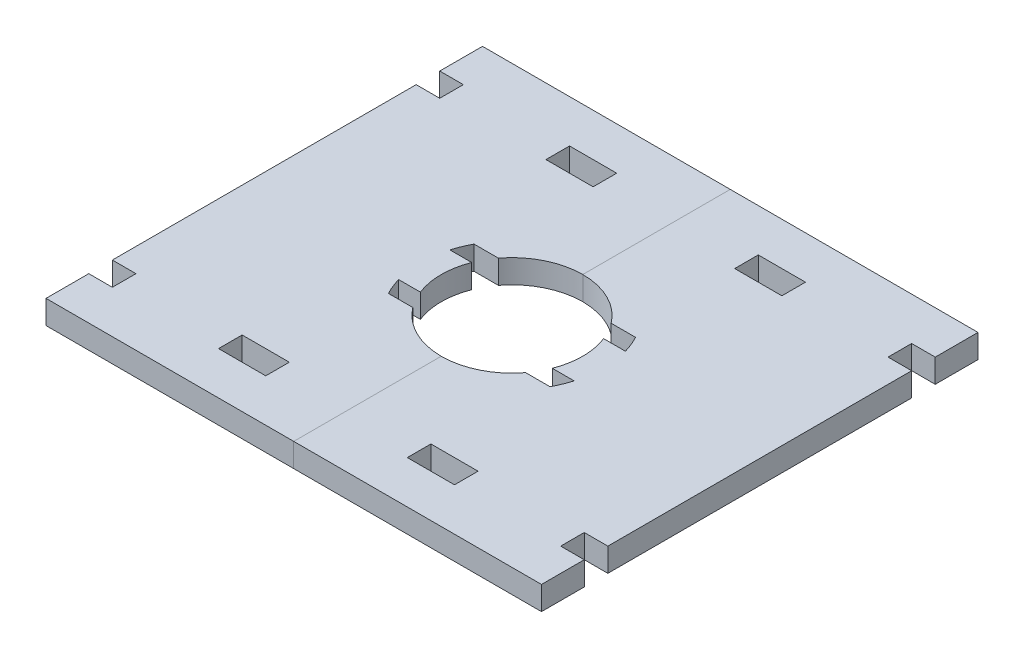
SolidWorks part; units mm, degrees
ref_plane "Front Plane" through (0, 0, 0) normal (0, 0, 1) x (1, 0, 0)
ref_plane "Top Plane" through (0, 0, 0) normal (0, 1, 0) x (1, 0, 0)
ref_plane "Right Plane" through (0, 0, 0) normal (1, 0, 0) x (0, 0, -1)
sketch "Sketch1" plane through (0, 0, 0) normal (0, 1, 0) x (1, 0, 0)
  line L0 (-15.5, 7.25) -> (-13.6999, 7.25) construction
  line L1 (-13.6999, -7.25) -> (-9.5623, -7.25)
  line L2 (-15.5, -7.25) -> (-15.5, -4.35) construction
  line L3 (-13.6999, 7.25) -> (-9.5623, 7.25)
  line L4 (15.5, 4.35) -> (15.5, 7.25) construction
  line L5 (-14.04, -6.5671) -> (-10.8697, -5.0842) construction
  line L6 (-14.04, 6.5671) -> (-10.8697, 5.0842) construction
  line L7 (-14.8771, -4.35) -> (-11.1838, -4.35)
  line L8 (-15.5, -4.35) -> (-15.5, 0) construction
  line L9 (-14.8771, 4.35) -> (-11.1838, 4.35)
  line L10 (15.5, 0) -> (15.5, 4.35) construction
  line L11 (-14.9234, -4.1882) -> (14.9234, 4.1882) construction
  line L12 (-14.9234, 4.1882) -> (14.9234, -4.1882) construction
  line L13 (-15.5, 7.25) -> (-14.04, 6.5671) construction
  line L14 (-15.5, 4.35) -> (-15.5, 7.25) construction
  line L15 (-15.5, 4.35) -> (-14.8771, 4.35) construction
  line L16 (-15.5, 4.35) -> (-14.9234, 4.1882) construction
  line L17 (-15.5, 0) -> (-15.5, 4.35) construction
  line L18 (-15.5, 0) -> (-15.5, 4.35) construction
  line L19 (-15.5, -4.35) -> (-15.5, 0) construction
  line L20 (-15.5, -4.35) -> (-14.9234, -4.1882) construction
  line L21 (-15.5, -4.35) -> (-14.8771, -4.35) construction
  line L22 (-15.5, -7.25) -> (-14.04, -6.5671) construction
  line L23 (-15.5, -7.25) -> (-13.6999, -7.25) construction
  line L24 (15.5, -7.25) -> (15.5, -4.35) construction
  line L25 (14.04, -6.5671) -> (15.5, -7.25) construction
  line L26 (13.6999, -7.25) -> (15.5, -7.25) construction
  line L27 (15.5, -4.35) -> (15.5, 0) construction
  line L28 (15.5, -4.35) -> (15.5, 0) construction
  line L29 (15.5, 0) -> (15.5, 4.35) construction
  line L30 (14.9234, 4.1882) -> (15.5, 4.35) construction
  line L31 (14.8771, 4.35) -> (15.5, 4.35) construction
  line L32 (13.6999, 7.25) -> (15.5, 7.25) construction
  line L33 (14.9234, -4.1882) -> (15.5, -4.35) construction
  line L34 (14.8771, -4.35) -> (15.5, -4.35) construction
  line L35 (-9.5623, 7.25) -> (9.5623, 7.25) construction
  line L36 (9.5623, 7.25) -> (13.6999, 7.25)
  line L37 (-9.3, 4.35) -> (9.3, 4.35) construction
  line L38 (11.1838, 4.35) -> (14.8771, 4.35)
  line L39 (-10.8697, 5.0842) -> (-9.3, 4.35) construction
  line L40 (-9.3, 4.35) -> (9.3, -4.35) construction
  line L41 (-11.1838, 4.35) -> (-9.3, 4.35) construction
  line L42 (-9.5623, -7.25) -> (9.5623, -7.25) construction
  line L43 (9.5623, -7.25) -> (13.6999, -7.25)
  line L44 (-9.3, -4.35) -> (9.3, -4.35) construction
  line L45 (11.1838, -4.35) -> (14.8771, -4.35)
  line L46 (-10.8697, -5.0842) -> (-9.3, -4.35) construction
  line L47 (-9.3, -4.35) -> (9.3, 4.35) construction
  line L48 (-11.1838, -4.35) -> (-9.3, -4.35) construction
  line L49 (9.3, -4.35) -> (11.1838, -4.35) construction
  line L50 (9.3, -4.35) -> (10.8697, -5.0842) construction
  line L51 (10.8697, -5.0842) -> (14.04, -6.5671) construction
  line L52 (9.3, 4.35) -> (11.1838, 4.35) construction
  line L53 (9.3, 4.35) -> (10.8697, 5.0842) construction
  line L54 (10.8697, 5.0842) -> (15.5, 7.25) construction
  arc A0 (-11.1838, 4.35) -> (-11.1838, -4.35) centre (0, 0) ccw
  arc A1 (-13.6999, 7.25) -> (-14.9234, 4.1882) centre (0, 0) ccw
  arc A2 (13.6999, 7.25) -> (-13.6999, 7.25) centre (0, 0) ccw construction
  arc A3 (-13.6999, -7.25) -> (13.6999, -7.25) centre (0, 0) ccw construction
  arc A4 (13.6999, -7.25) -> (14.9234, -4.1882) centre (0, 0) ccw
  arc A5 (15.5, 0) -> (14.9234, 4.1882) centre (0, 0) ccw construction
  arc A6 (14.9234, 4.1882) -> (13.6999, 7.25) centre (0, 0) ccw
  arc A7 (14.9234, -4.1882) -> (15.5, 0) centre (0, 0) ccw construction
  arc A8 (-14.9234, 4.1882) -> (-15.5, 0) centre (0, 0) ccw construction
  arc A9 (-14.9234, -4.1882) -> (-13.6999, -7.25) centre (0, 0) ccw
  arc A10 (-15.5, 0) -> (-14.9234, -4.1882) centre (0, 0) ccw construction
  arc A11 (-9.5623, 7.25) -> (-10.8697, 5.0842) centre (0, 0) ccw construction
  arc A12 (-10.8697, 5.0842) -> (-11.1838, 4.35) centre (0, 0) ccw construction
  arc A13 (-10.8697, -5.0842) -> (-9.5623, -7.25) centre (0, 0) ccw construction
  arc A14 (-9.5623, -7.25) -> (9.5623, -7.25) centre (0, 0) ccw
  arc A15 (-11.1838, -4.35) -> (-10.8697, -5.0842) centre (0, 0) ccw construction
  arc A16 (10.8697, -5.0842) -> (11.1838, -4.35) centre (0, 0) ccw construction
  arc A17 (11.1838, -4.35) -> (-9.5623, 7.25) centre (0, 0) ccw
  arc A18 (9.5623, -7.25) -> (10.8697, -5.0842) centre (0, 0) ccw construction
  dimension "D1" = 24
  dimension "D2" = 31
  dimension "D3" = 14.5
  dimension "D4" = 8.7
sketch "Sketch2" plane through (0, 0, 0) normal (0, 1, 0) x (1, 0, 0)
  line L0 (11.1838, -4.35) -> (14.8771, -4.35) construction
  line L1 (-13.6999, 7.25) -> (-9.5623, 7.25) construction
  line L2 (-14.8771, -4.35) -> (-11.1838, -4.35) construction
  line L3 (-14.8771, 4.35) -> (-11.1838, 4.35) construction
  line L4 (9.5623, -7.25) -> (13.6999, -7.25) construction
  line L5 (-13.6999, -7.25) -> (-9.5623, -7.25) construction
  line L6 (9.5623, 7.25) -> (13.6999, 7.25) construction
  line L7 (11.1838, 4.35) -> (14.8771, 4.35) construction
  line L8 (11.1838, -4.35) -> (14.8771, -4.35)
  line L9 (-13.6999, 7.25) -> (-9.5623, 7.25)
  line L10 (-14.8771, -4.35) -> (-11.1838, -4.35)
  line L11 (-14.8771, 4.35) -> (-11.1838, 4.35)
  line L12 (9.5623, -7.25) -> (13.6999, -7.25)
  line L13 (-13.6999, -7.25) -> (-9.5623, -7.25)
  line L14 (9.5623, 7.25) -> (13.6999, 7.25)
  line L15 (11.1838, 4.35) -> (14.8771, 4.35)
  line L17 (-42, -37) -> (42, -37)
  line L18 (-42, -37) -> (-42, 37)
  line L19 (-42, 37) -> (42, 37)
  line L20 (42, -37) -> (42, 37)
  line L21 (-42, -37) -> (42, 37) construction
  line L22 (-42, 37) -> (42, -37) construction
  arc A0 (11.1838, -4.35) -> (-9.5623, 7.25) centre (0, 0) ccw construction
  arc A1 (-13.6999, 7.25) -> (-14.9234, 4.1882) centre (0, 0) ccw construction
  arc A2 (-11.1838, 4.35) -> (-11.1838, -4.35) centre (0, 0) ccw construction
  arc A3 (13.6999, -7.25) -> (14.9234, -4.1882) centre (0, 0) ccw construction
  arc A4 (-9.5623, -7.25) -> (9.5623, -7.25) centre (0, 0) ccw construction
  arc A5 (-14.9234, -4.1882) -> (-13.6999, -7.25) centre (0, 0) ccw construction
  arc A6 (14.9234, 4.1882) -> (13.6999, 7.25) centre (0, 0) ccw construction
  arc A7 (11.1838, -4.35) -> (-9.5623, 7.25) centre (0, 0) ccw
  arc A8 (-13.6999, 7.25) -> (-14.9234, 4.1882) centre (0, 0) ccw
  arc A9 (-11.1838, 4.35) -> (-11.1838, -4.35) centre (0, 0) ccw
  arc A10 (13.6999, -7.25) -> (14.9234, -4.1882) centre (0, 0) ccw
  arc A11 (-9.5623, -7.25) -> (9.5623, -7.25) centre (0, 0) ccw
  arc A12 (-14.9234, -4.1882) -> (-13.6999, -7.25) centre (0, 0) ccw
  arc A13 (14.9234, 4.1882) -> (13.6999, 7.25) centre (0, 0) ccw
  dimension "D1" = 84
  dimension "D2" = 74
extrude "Boss-Extrude1" add sketch "Sketch2" along normal blind 4 contours L17 L20 L19 L18 A13 L15 A7 L8 A10 L12 A11 L13 A12 L10 A9 L11 A8 L9 L14 region at (-40.8805, 0, 0)
split "Split1" trim tools "Right Plane" bodies to split 101 resulting bodies 102 103
sketch "Sketch4" plane through (0, 4, 0) normal (0, 1, 0) x (1, 0, 0)
  line L0 (0, -18.5) -> (42, -18.5) construction
  line L2 (42, -37) -> (42, 37) construction
  line L3 (0, -18.5) -> (0, -37) construction
  line L4 (-42, -37) -> (-42, 37) construction
  line L5 (-20, -29.75) -> (-12, -29.75)
  line L6 (-20, -29.75) -> (-20, -25.75)
  line L7 (-20, -25.75) -> (-12, -25.75)
  line L8 (-12, -29.75) -> (-12, -25.75)
  line L9 (-20, -29.75) -> (-12, -25.75) construction
  line L10 (-20, -25.75) -> (-12, -29.75) construction
  line L11 (-42, -29.75) -> (-38, -29.75)
  line L12 (-42, -29.75) -> (-42, -25.75)
  line L13 (-42, -25.75) -> (-38, -25.75)
  line L14 (-38, -29.75) -> (-38, -25.75)
  line L15 (-42, -29.75) -> (-38, -25.75) construction
  line L16 (-42, -25.75) -> (-38, -29.75) construction
  line L17 (0, 0) -> (0, -37) construction
  line L33 (42, -25.75) -> (38, -29.75) construction
  line L34 (42, -29.75) -> (38, -25.75) construction
  line L35 (20, -25.75) -> (12, -29.75) construction
  line L36 (20, -29.75) -> (12, -25.75) construction
  line L45 (38, -29.75) -> (38, -25.75)
  line L46 (42, -25.75) -> (38, -25.75)
  line L47 (42, -29.75) -> (42, -25.75)
  line L48 (42, -29.75) -> (38, -29.75)
  line L49 (12, -29.75) -> (12, -25.75)
  line L50 (20, -25.75) -> (12, -25.75)
  line L51 (20, -29.75) -> (20, -25.75)
  line L52 (20, -29.75) -> (12, -29.75)
  line L53 (-2.2, 0) -> (2.2, 0) construction
  line L54 (20, 29.75) -> (12, 25.75) construction
  line L55 (20, 25.75) -> (12, 29.75) construction
  line L56 (42, 29.75) -> (38, 25.75) construction
  line L57 (42, 25.75) -> (38, 29.75) construction
  line L58 (20, 29.75) -> (12, 29.75)
  line L59 (20, 29.75) -> (20, 25.75)
  line L60 (20, 25.75) -> (12, 25.75)
  line L61 (12, 29.75) -> (12, 25.75)
  line L62 (42, 29.75) -> (38, 29.75)
  line L63 (42, 29.75) -> (42, 25.75)
  line L64 (42, 25.75) -> (38, 25.75)
  line L65 (38, 29.75) -> (38, 25.75)
  line L82 (-42, 25.75) -> (-38, 29.75) construction
  line L83 (-42, 29.75) -> (-38, 25.75) construction
  line L84 (-20, 25.75) -> (-12, 29.75) construction
  line L85 (-20, 29.75) -> (-12, 25.75) construction
  line L94 (-38, 29.75) -> (-38, 25.75)
  line L95 (-42, 25.75) -> (-38, 25.75)
  line L96 (-42, 29.75) -> (-42, 25.75)
  line L97 (-42, 29.75) -> (-38, 29.75)
  line L98 (-12, 29.75) -> (-12, 25.75)
  line L99 (-20, 25.75) -> (-12, 25.75)
  line L100 (-20, 29.75) -> (-20, 25.75)
  line L101 (-20, 29.75) -> (-12, 29.75)
  point P6 (-16, -27.75)
  point P14 (0, -27.75)
  point P15 (-40, -27.75)
  point P53 (40, -27.75)
  point P54 (16, -27.75)
  point P65 (16, 27.75)
  point P66 (40, 27.75)
  point P95 (-40, 27.75)
  point P96 (-16, 27.75)
  dimension "D1" = 4
  dimension "D2" = 8
  dimension "D3" = 20
  dimension "D4" = 4
extrude "Cut-Extrude2" cut sketch "Sketch4" against normal through all both
equation "\"m3_hole\"= 3.5"
equation "\"m3_washer\"= 7.3"
equation "\"m3_nut\"= 5.3"
equation "\"guide_width\"= 10.0"
equation "\"guide_length\"= 65.0"
equation "\"guide_tab_length\" = 10.0"
equation "\"guide_tab_width\" = 9.0"
equation "\"guide_thickness\" = 12.0"
equation "\"grinder_od\"= 52.0"
equation "\"grinder_id\"= 45.5"
equation "\"grinder_adjust_od\" = 58.0"
equation "\"funnel_width_from_adjust_ring\" = 13.0"
equation "\"drill_contact_diameter_small\" = 24.0"
equation "\"drill_contact_diameter_medium\" = 28.0"
equation "\"drill_contact_diameter_large\" = 39.0"
equation "\"drill_contact_diameter_tab\" = 31.0"
equation "\"drill_contact_ow_tab\" = 14.5"
equation "\"drill_contact_iw_tab\" = 8.7"
equation "\"drill_contact_small_height\" = 15.5"
equation "\"drill_contact_large_height\" = 34.5"
equation "\"D1@Sketch1\"=\"drill_contact_diameter_small\""
equation "\"D2@Sketch1\"=\"drill_contact_diameter_tab\""
equation "\"D3@Sketch1\"=\"drill_contact_ow_tab\""
equation "\"D1@Sketch2\"=\"grinder_od\"+\"guide_thickness\"+20"
equation "\"D2@Sketch2\"=\"grinder_od\"+\"guide_thickness\"+\"guide_tab_length\""
equation "\"plywood_thickness\" = 4.0"
equation "\"D4@Sketch1\"=\"drill_contact_iw_tab\""
equation "\"plywood_peg_length\" = 40.0"
equation "\"plywood_peg_width\" = 8.0"
equation "\"D3@Sketch4\"=\"plywood_peg_length\"/2"
equation "\"D2@Sketch4\"=\"plywood_peg_width\""
equation "\"D1@Sketch4\"=\"plywood_thickness\""
equation "\"D4@Sketch4\"=\"plywood_thickness\""
